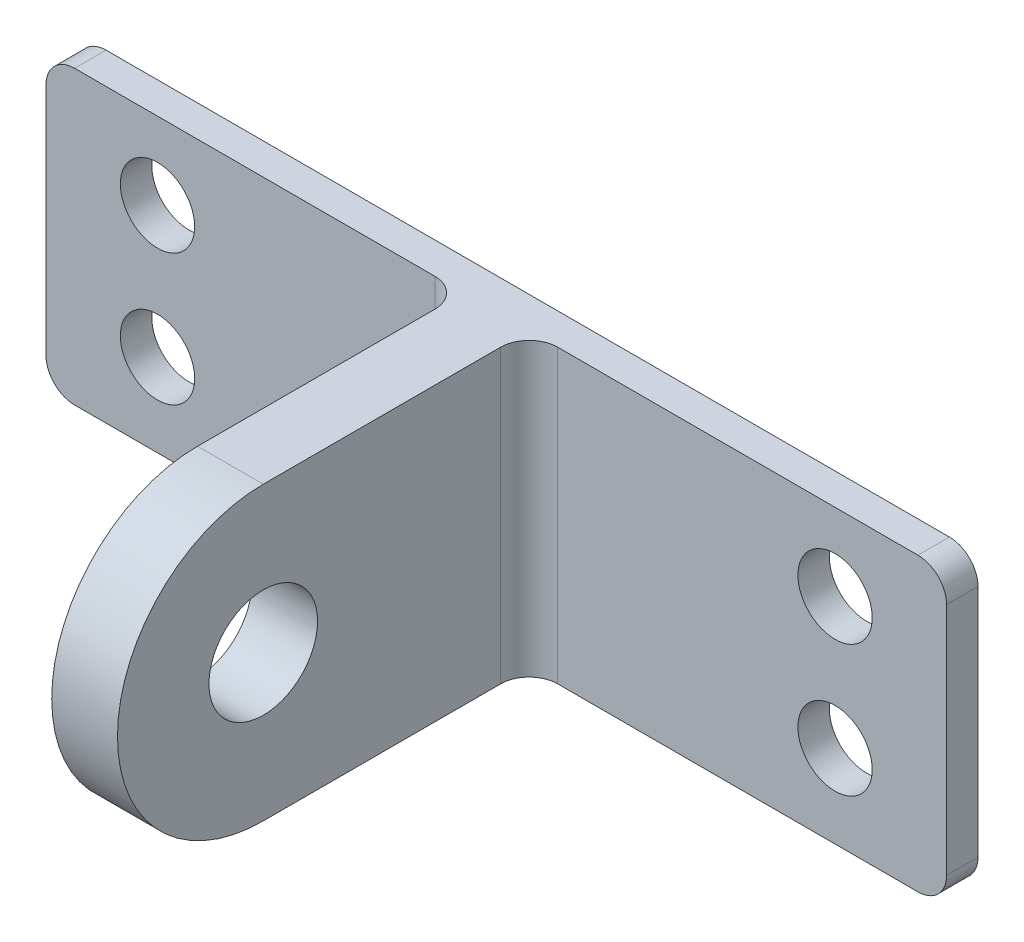
SolidWorks part; units mm, degrees
material "Cast Carbon Steel"
ref_plane "Front Plane" through (0, 0, 0) normal (0, 0, 1) x (1, 0, 0)
ref_plane "Top Plane" through (0, 0, 0) normal (0, 1, 0) x (1, 0, 0)
ref_plane "Right Plane" through (0, 0, 0) normal (1, 0, 0) x (0, 0, -1)
sketch "Sketch1" plane through (0, 0, 0) normal (0, 0, 1) x (1, 0, 0)
  line L1 (-0.9481, -25.3366) -> (79.0619, -25.3366)
  line L2 (-0.9481, -25.3366) -> (-0.9481, 0.5714)
  line L3 (-0.9481, 0.5714) -> (79.0619, 0.5714)
  line L4 (79.0619, -25.3366) -> (79.0619, 0.5714)
  line L5 (36.1359, 0.5714) -> (36.1359, -25.3366)
  line L6 (41.9779, 0.5714) -> (41.9779, -25.3366)
  line L7 (-0.9481, 0.5714) -> (8.9579, 0.5714)
  line L8 (-0.9481, 0.5714) -> (-0.9481, -5.1915)
  circle A0 centre (8.9579, -6.2866) radius 3.302
  circle A1 centre (69.1559, -6.2866) radius 3.302
  circle A2 centre (69.1559, -17.9706) radius 3.302
  circle A3 centre (8.9579, -17.9706) radius 3.302
  dimension "D1" = 25.908
  dimension "D2" = 80.01
extrude "Boss-Extrude1" add sketch "Sketch1" along normal blind 2.794 contours L5 L3 L2 L1 A0 A3 | L3 L6 L1 L4 A2 A1 region at (18.257, -12.4021, 0) region at (59.8569, -12.4021, 0)
extrude "Boss-Extrude2" add sketch "Sketch1<7>" along normal blind 39.624 contours L6 L3 L5 L1 region at (39.0569, -12.3826, 0)
sketch "Sketch1<7>" plane through (0, 0, 0) normal (0, 0, 1) x (1, 0, 0) same geometry as "Sketch1"
fillet "Fillet1" radius 2.54 4 edges at (79.0619, 0.5714, 1.397) (79.0619, -25.3366, 1.397) (-0.9481, -25.3366, 1.397) (-0.9481, 0.5714, 1.397)
sketch "Sketch2" plane through (41.9779, 0, 0) normal (1, 0, 0) x (0, 0, -1)
  line L0 (-2.794, -12.3826) -> (-26.416, -12.3826)
  line L1 (-2.794, 0.5714) -> (-2.794, -25.3366) construction
  circle A0 centre (-26.416, -12.3826) radius 4.826
  circle A1 centre (-26.416, -12.3826) radius 12.954
  line M3 (-2.794, 0.5714) -> (-39.624, 0.5714)
  line M4 (-39.624, 0.5714) -> (-39.624, -25.3366)
  line M5 (-39.624, -25.3366) -> (-2.794, -25.3366)
extrude "Cut-Extrude4" cut sketch "Sketch2" against normal blind 39.624 contours A0
extrude "Cut-Extrude5" cut sketch "Sketch2<11>" against normal blind 39.624 contours A1 M3 M4 M5 region at (41.9779, -12.3826, 39.3991)
sketch "Sketch2<11>" plane through (41.9779, 0, 0) normal (1, 0, 0) x (0, 0, -1) same geometry as "Sketch2"
fillet "Fillet2" radius 2.54 2 edges at (36.1359, -12.3826, 2.794) (41.9779, -12.3826, 2.794)
